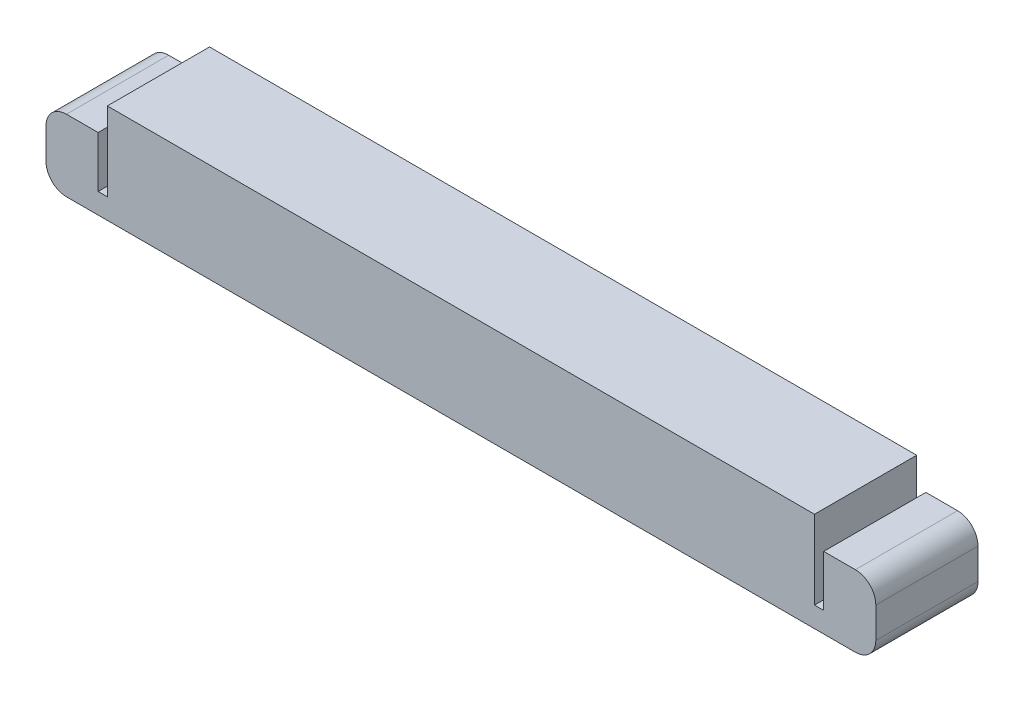
SolidWorks part; units mm, degrees
ref_plane "Front Plane" through (0, 0, 0) normal (0, 0, 1) x (1, 0, 0)
ref_plane "Top Plane" through (0, 0, 0) normal (0, 1, 0) x (1, 0, 0)
ref_plane "Right Plane" through (0, 0, 0) normal (1, 0, 0) x (0, 0, -1)
ref_axis "X Axis" through (-39.3295, 0, 0) along (1, 0, 0)
ref_axis "Y Axis" through (0, 0, -37.7472) along (0, 0, 1)
ref_axis "Z Axis" through (0, 35.6627, 0) along (0, -1, 0)
sketch "Sketch1" plane through (0, 0, 0) normal (0, 1, 0) x (1, 0, 0)
  line L0 (0, 75) -> (0, -75) construction
  line L2 (-86.5, 62.5) -> (86.5, 62.5)
  line L3 (-86.5, 62.5) -> (-86.5, 87.5)
  line L4 (-86.5, 87.5) -> (86.5, 87.5)
  line L5 (86.5, 62.5) -> (86.5, 87.5)
  line L6 (-86.5, 62.5) -> (86.5, 87.5) construction
  line L7 (-86.5, 87.5) -> (86.5, 62.5) construction
  line L17 (-35, 0) -> (35, 0) construction
  point P2 (0, 0)
  point P22 (0, 0)
  dimension "D1" = 150
  dimension "D2" = 173
  dimension "D3" = 25
extrude "Boss-Extrude1" add sketch "Sketch1" against normal blind 5 and the other way blind 19.25
sketch "Sketch2" plane through (0, -5, 0) normal (0, 1, 0) x (1, 0, 0)
  line L1 (-86.5, 87.5) -> (-101.5, 87.5)
  line L2 (-86.5, 87.5) -> (-86.5, 62.5)
  line L3 (-86.5, 62.5) -> (-101.5, 62.5)
  line L4 (-101.5, 87.5) -> (-101.5, 62.5)
  line L5 (86.5, 87.5) -> (101.5, 87.5)
  line L6 (86.5, 87.5) -> (86.5, 62.5)
  line L7 (86.5, 62.5) -> (101.5, 62.5)
  line L8 (101.5, 87.5) -> (101.5, 62.5)
  dimension "D1" = 15
extrude "Boss-Extrude2" add sketch "Sketch2" along normal up to surface (5 mm away) up to plane "Top Plane"
sketch "Sketch3" plane through (0, 0, 0) normal (0, 1, 0) x (1, 0, 0)
  line L0 (-101.5, 62.5) -> (-86.5, 62.5) construction
  line L1 (-101.5, 87.5) -> (-88.75, 87.5)
  line L2 (-101.5, 87.5) -> (-101.5, 62.5)
  line L3 (-101.5, 62.5) -> (-88.75, 62.5)
  line L4 (-88.75, 87.5) -> (-88.75, 62.5)
  line L5 (-86.5, 62.5) -> (-86.5, 87.5) construction
  line L6 (101.5, 87.5) -> (88.75, 87.5)
  line L7 (101.5, 87.5) -> (101.5, 62.5)
  line L8 (101.5, 62.5) -> (88.75, 62.5)
  line L9 (88.75, 87.5) -> (88.75, 62.5)
  line L18 (101.5, 62.5) -> (101.5, 87.5) construction
  dimension "D1" = 2.25
extrude "Boss-Extrude3" add sketch "Sketch3" along normal blind 12.5
fillet "Fillet1" radius 5 4 edges at (101.5, -5, -75) (101.5, 12.5, -75) (-101.5, -5, -75) (-101.5, 12.5, -75)
